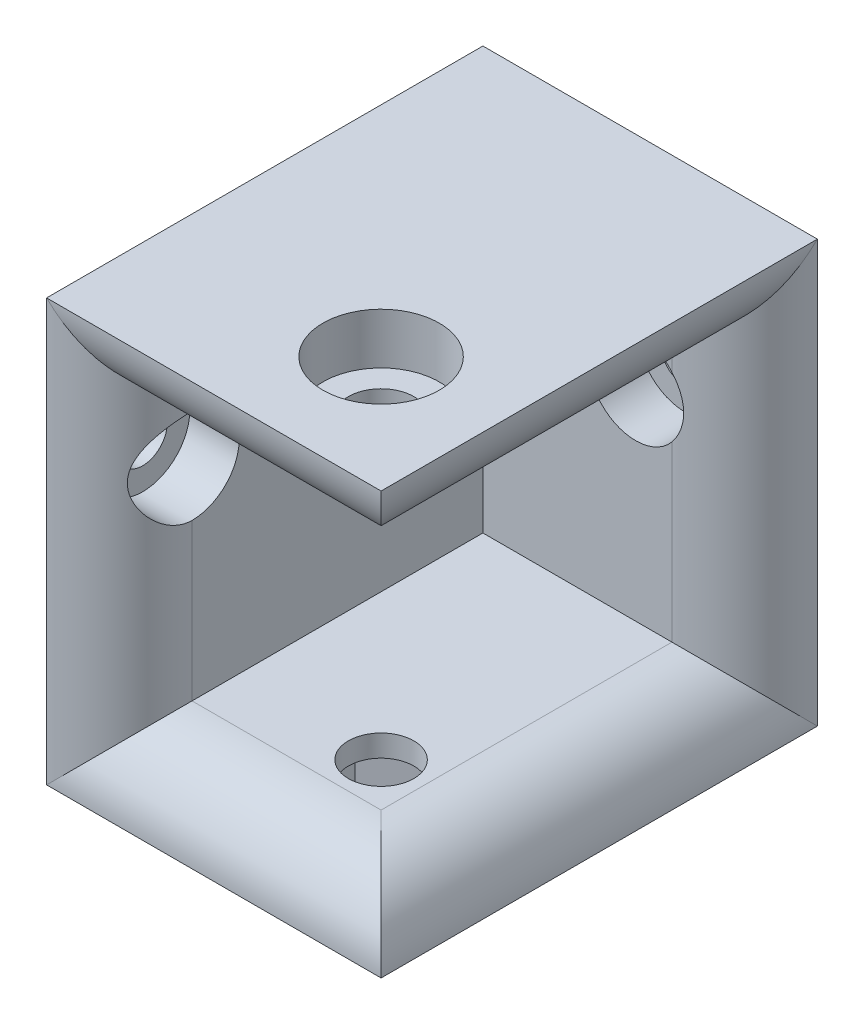
SolidWorks part; units mm, degrees
material "ABS"
ref_plane "Front Plane" through (0, 0, 0) normal (0, 0, 1) x (1, 0, 0)
ref_plane "Top Plane" through (0, 0, 0) normal (0, 1, 0) x (1, 0, 0)
ref_plane "Right Plane" through (0, 0, 0) normal (1, 0, 0) x (0, 0, -1)
sketch "Sketch1" plane through (0, 0, 0) normal (0, 1, 0) x (1, 0, 0)
  line L1 (0, 0) -> (23, 0)
  line L2 (0, 0) -> (0, 30)
  line L3 (0, 30) -> (23, 30)
  line L4 (23, 0) -> (23, 30)
  dimension "D1" = 23
  dimension "D2" = 30
extrude "Boss-Extrude1" add sketch "Sketch1" along normal blind 5
sketch "Sketch22" plane through (0, 5, 0) normal (0, 1, 0) x (1, 0, 0)
  line L0 (0, 0) -> (5, 0)
  line L1 (0, 0) -> (23, 0) construction
  line L2 (23, 30) -> (23, 25)
  line L3 (23, 0) -> (23, 30) construction
  line L4 (5, 0) -> (5, 25)
  line L5 (5, 25) -> (23, 25)
  line L6 (0, 30) -> (23, 30)
  line L7 (0, 30) -> (0, 0)
  dimension "D1" = 5
  dimension "D2" = 5
extrude "Boss-Extrude3" add sketch "Sketch22" along normal blind 24
hole_wizard "CBORE for M3 Hex Socket Head Cap Screw6" positions "Sketch29" profile "Sketch30" counterbore size "M3" standard "ISO" end condition through all
sketch "Sketch29" plane through (0, 0, -25) normal (0, 0, 1) x (1, 0, 0)
  line L2 (23, 29) -> (23, 5) construction
  line L3 (5, 29) -> (23, 29) construction
  point P13 (15.5, 19)
  dimension "D1" = 10
  dimension "D2" = 7.5
sketch "Sketch30" plane through (15.5, 19, -25) normal (1, 0, 0) x (0, -1, 0)
  line L0 (0, 0) -> (0, 5)
  line L1 (0, 5) -> (1.7, 5)
  line L3 (1.7, 5) -> (1.7, 3.4)
  line L4 (1.7, 3.4) -> (3.25, 3.4)
  line L5 (3.25, 3.4) -> (3.25, 0)
  line L7 (3.25, 0) -> (0, 0)
  line L11 (0, -6.35) -> (0, 107.95) construction
  dimension "Thru Hole Dia." = 3.4
  dimension "Thru Hole Depth" = 5
  dimension "C'Bore Dia." = 6.5
  dimension "C'Bore Depth" = 3.4
hole_wizard "CBORE for M3 Hex Socket Head Cap Screw7" positions "Sketch31" profile "Sketch32" counterbore size "M3" standard "ISO" end condition through all
sketch "Sketch31" plane through (5, 0, 0) normal (1, 0, 0) x (0, 0, -1)
  line L0 (0, 29) -> (0, 5) construction
  line L2 (25, 29) -> (25, 5) construction
  line L4 (0, 29) -> (25, 29) construction
  point P0 (5, 19)
  point P2 (20, 19)
  dimension "D1" = 5
  dimension "D2" = 10
  dimension "D3" = 10
  dimension "D4" = 5
sketch "Sketch32" plane through (5, 19, -5) normal (0, 1, 0) x (0, 0, -1)
  line L0 (0, 0) -> (0, 5)
  line L1 (0, 5) -> (1.7, 5)
  line L3 (1.7, 5) -> (1.7, 3.4)
  line L4 (1.7, 3.4) -> (3.25, 3.4)
  line L5 (3.25, 3.4) -> (3.25, 0)
  line L7 (3.25, 0) -> (0, 0)
  line L11 (0, -6.35) -> (0, 107.95) construction
  dimension "Thru Hole Dia." = 3.4
  dimension "Thru Hole Depth" = 5
  dimension "C'Bore Dia." = 6.5
  dimension "C'Bore Depth" = 3.4
sketch "Sketch33" plane through (0, 0, -25) normal (0, 0, 1) x (1, 0, 0)
  line L0 (23, 29) -> (23, 5) construction
  line L1 (5, 29) -> (23, 29)
  line L2 (5, 29) -> (5, 24)
  line L3 (5, 24) -> (23, 24)
  line L4 (23, 29) -> (23, 24)
  dimension "D1" = 5
extrude "Boss-Extrude4" add sketch "Sketch33" along normal up to surface (25 mm away) up to face at (9.3333, 11.3333, 0)
hole_wizard "CBORE for M4 Hex Socket Head Cap Screw1" positions "Sketch34" profile "Sketch35" counterbore size "M4" standard "ISO" end condition up to next
sketch "Sketch34" plane through (0, 29, 0) normal (0, 1, 0) x (1, 0, 0)
  line L0 (23, 30) -> (0, 30) construction
  line L1 (0, 30) -> (0, 0) construction
  point P0 (15, 8)
  dimension "D1" = 22
  dimension "D2" = 15
sketch "Sketch35" plane through (15, 29, -8) normal (1, 0, 0) x (0, 0, 1)
  line L0 (0, 0) -> (0, 5)
  line L1 (0, 5) -> (2.25, 5)
  line L3 (2.25, 5) -> (2.25, 3.5)
  line L4 (2.25, 3.5) -> (4, 3.5)
  line L5 (4, 3.5) -> (4, 0)
  line L7 (4, 0) -> (0, 0)
  line L11 (0, -6.35) -> (0, 107.95) construction
  dimension "Thru Hole Dia." = 4.5
  dimension "Thru Hole Depth" = 5
  dimension "C'Bore Dia." = 8
  dimension "C'Bore Depth" = 3.5
sketch "Sketch36" plane through (0, 5, 0) normal (0, 1, 0) x (1, 0, 0)
  line L0 (0, 30) -> (0, 0) construction
  line L2 (23, 30) -> (0, 30) construction
  circle A0 centre (15, 8) radius 2.25
  dimension "D1" = 4.5
  dimension "D2" = 15
  dimension "D3" = 22
extrude "Cut-Extrude1" cut sketch "Sketch36" against normal through all
sketch "Sketch37" plane through (0, 0, 0) normal (0, -1, 0) x (1, 0, 0)
  line L7 (15, -12.9075) -> (19.25, -10.4537)
  line L8 (19.25, -10.4537) -> (19.25, -5.5463)
  line L9 (19.25, -5.5463) -> (15, -3.0925)
  line L10 (15, -3.0925) -> (10.75, -5.5463)
  line L11 (10.75, -5.5463) -> (10.75, -10.4537)
  line L12 (10.75, -10.4537) -> (15, -12.9075)
  circle A0 centre (15, -8) radius 4.25 construction
  dimension "D1" = 8.5
extrude "Cut-Extrude2" cut sketch "Sketch37" against normal blind 3.5
fillet "Fillet1" radius 5 6 edges at (14, 24, 0) (23, 24, -12.5) (23, 14.5, -25) (23, 5, -12.5) (14, 5, 0) (5, 14.5, 0)
ref_plane "Plane1" through (0, 0, 0) normal (0, 0, -1) x (-1, 0, 0)
mirror "Mirror1" [suppressed] about plane through (0, 0, 0) normal (0, 0, -1) of bodies 122
delete or keep bodies "Body-Delete/Keep 1" [suppressed] type delete bodies bodies 122
